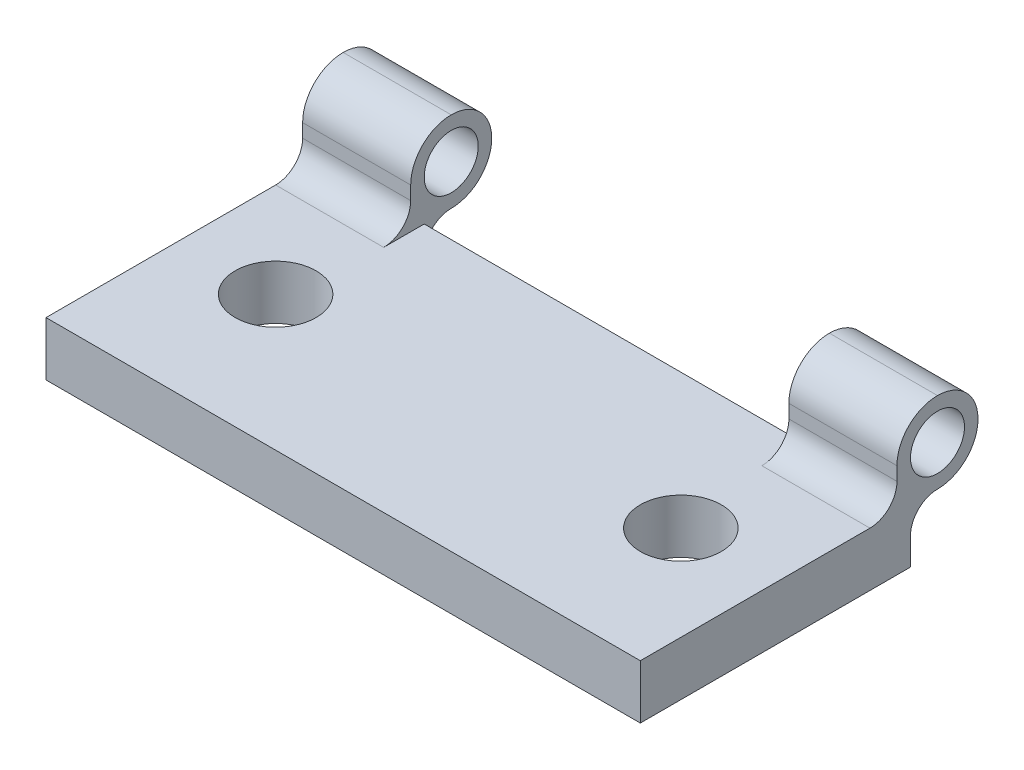
SolidWorks part; units mm, degrees
ref_plane "Front Plane" through (0, 0, 0) normal (0, 0, 1) x (1, 0, 0)
ref_plane "Top Plane" through (0, 0, 0) normal (0, 1, 0) x (1, 0, 0)
ref_plane "Right Plane" through (0, 0, 0) normal (1, 0, 0) x (0, 0, -1)
sketch "Sketch2" plane through (0, 0, 0) normal (0, 1, 0) x (1, 0, 0)
  line L1 (-11, 5) -> (11, 5)
  line L2 (-11, 5) -> (-11, -5)
  line L3 (-11, -5) -> (11, -5)
  line L4 (11, 5) -> (11, -5)
  line L5 (-11, 5) -> (11, -5) construction
  line L6 (-11, -5) -> (11, 5) construction
  circle A0 centre (-7.5, 0) radius 1.5
  circle A1 centre (7.5, 0) radius 1.5
  point P0 (0, 0)
  point P10 (7.7935, 0)
  dimension "D3" = 15
  dimension "D4" = 0
  dimension "D5" = 3
  dimension "D6" = 5
  dimension "D7" = 7.5
  dimension "D1" = 22
  dimension "D2" = 10
extrude "Boss-Extrude1" add sketch "Sketch2" along normal blind 2
sketch "Sketch3" plane through (11, 0, 0) normal (1, 0, 0) x (0, 0, -1)
  line L0 (4.5, 2) -> (4.5, 5)
  line L1 (4.5, 2) -> (7.5, 2)
  line L2 (4.5, 5) -> (7.5, 5)
  line L3 (7.5, 5) -> (7.5, 2)
  line L10 (4.5, 3.5) -> (4.5, 2)
  line L11 (-5, 2) -> (5, 2) construction
  line L12 (5, 2) -> (5, 0) construction
  circle A0 centre (6, 3.5) radius 1
  point P3 (5.7002, 3.5519)
  point P4 (0, 0)
  line M6 (5, 2) -> (-5, 2)
  dimension "D1" = 3
  dimension "D4" = 1.5
  dimension "D6" = 2
  dimension "D7" = 0.5
  dimension "D2" = 3
  dimension "D3" = 3
  dimension "D5" = 1.5
extrude "Boss-Extrude2" add sketch "Sketch3" against normal blind 4 contours L3 L2 L0 A0 M6 region at (11, 2.75, -4.5424)
mirror "Mirror1" about plane through (0, 0, 0) normal (1, 0, 0) of "Boss-Extrude2"
fillet "Fillet1" radius 1.5 4 edges at (9, 5, -7.5) (9, 5, -4.5) (-9, 5, -7.5) (-9, 5, -4.5)
fillet "Fillet2" radius 1 2 edges at (9, 2, -4.5) (-9, 2, -4.5)
fillet "Fillet3" radius 1 2 edges at (-9, 2, -5) (9, 2, -5)
fillet "Fillet4" radius 1.5 2 edges at (-9, 2, -7.5) (9, 2, -7.5)
